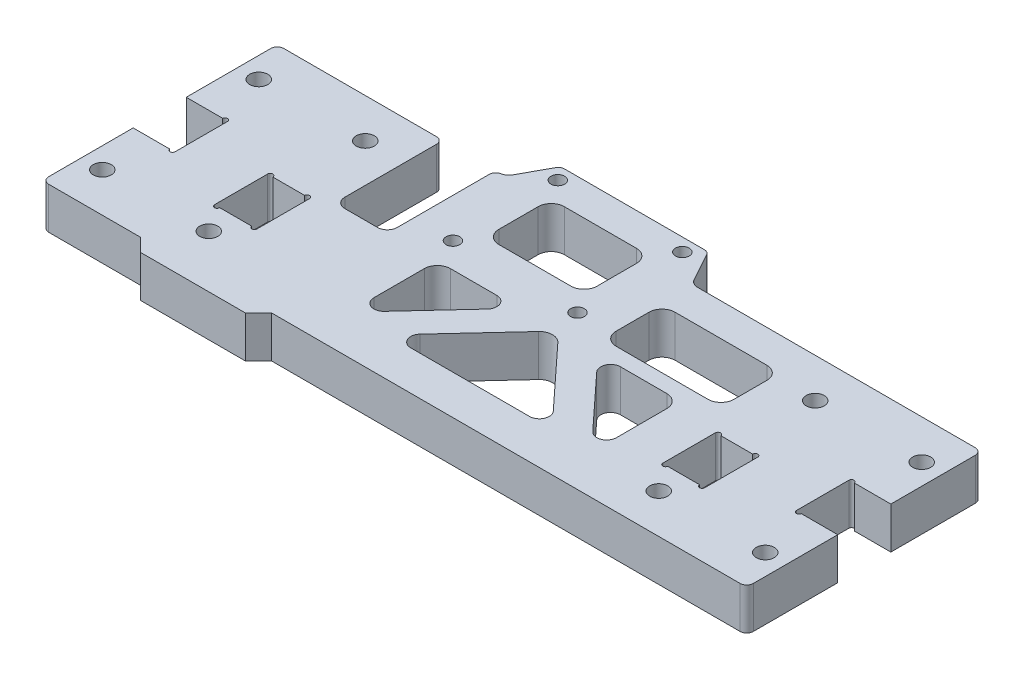
SolidWorks part; units mm, degrees
material "6061 Alloy"
ref_plane "Front Plane" through (0, 0, 0) normal (0, 0, 1) x (1, 0, 0)
ref_plane "Top Plane" through (0, 0, 0) normal (0, 1, 0) x (1, 0, 0)
ref_plane "Right Plane" through (0, 0, 0) normal (1, 0, 0) x (0, 0, -1)
sketch "Sketch1" plane through (0, 0, 0) normal (0, 1, 0) x (1, 0, 0)
  line L0 (107.5, 76.65) -> (107.5, 0) construction
  line L6 (32.7004, 36.1) -> (32.7004, 19.9)
  line L8 (45.6, 36) -> (45.6, 20)
  line L13 (0, 71.75) -> (69.5, 71.75)
  line L14 (69.5, 71.75) -> (75.5, 82.75)
  line L15 (75.5, 82.75) -> (120.5, 82.75)
  line L16 (120.5, 82.75) -> (126.5, 71.75)
  line L17 (126.5, 71.75) -> (215, 71.75)
  line L18 (32.7004, 28) -> (45.6, 28) construction
  line L19 (34.3004, 36.1) -> (44.0063, 36.1)
  line L20 (34.3004, 19.9) -> (44.0063, 19.9)
  line L21 (182.2996, 36.1) -> (182.2996, 19.9)
  line L22 (180.6996, 36.1) -> (170.9937, 36.1)
  line L23 (169.4, 36) -> (169.4, 20)
  line L24 (180.6996, 19.9) -> (170.9937, 19.9)
  line L25 (12.7, 35.875) -> (0, 35.875) construction
  line L29 (12.7, 43.975) -> (12.7, 27.775)
  line L30 (11.1189, 43.975) -> (0, 43.975)
  line L31 (11.1189, 27.775) -> (0, 27.775)
  line L32 (0, 27.775) -> (0, 0)
  line L33 (0, 43.975) -> (0, 71.75)
  line L34 (202.3, 35.875) -> (215, 35.875) construction
  line L35 (215, 43.975) -> (215, 71.75)
  line L36 (215, 27.775) -> (215, 0)
  line L37 (203.8811, 27.775) -> (215, 27.775)
  line L38 (203.8811, 43.975) -> (215, 43.975)
  line L39 (202.3, 43.975) -> (202.3, 27.775)
  line L40 (0, 0) -> (30, 0)
  line L41 (30, 0) -> (34, -4)
  line L42 (34, -4) -> (66, -4)
  line L43 (66, -4) -> (70, 0)
  line L44 (70, 0) -> (215, 0)
  circle A0 centre (38.85, 59.75) radius 2.75
  circle A5 centre (38.85, 12) radius 2.75
  circle A6 centre (176.15, 59.75) radius 2.75
  circle A7 centre (176.15, 12) radius 2.75
  arc A8 (32.7004, 36.1) -> (34.3004, 36.1) centre (33.5004, 36.1) cw
  arc A9 (45.6, 36) -> (44.0063, 36.1) centre (44.8, 36) ccw
  arc A10 (32.7004, 19.9) -> (34.3004, 19.9) centre (33.5004, 19.9) ccw
  arc A11 (45.6, 20) -> (44.0063, 19.9) centre (44.8, 20) cw
  arc A12 (182.2996, 19.9) -> (180.6996, 19.9) centre (181.4996, 19.9) cw
  arc A13 (182.2996, 36.1) -> (180.6996, 36.1) centre (181.4996, 36.1) ccw
  arc A14 (169.4, 36) -> (170.9937, 36.1) centre (170.2, 36) cw
  arc A15 (169.4, 20) -> (170.9937, 19.9) centre (170.2, 20) ccw
  circle A16 centre (6.35, 12) radius 2.75
  circle A17 centre (6.35, 59.75) radius 2.75
  arc A18 (12.7, 27.775) -> (11.1189, 27.775) centre (11.9095, 27.8976) cw
  arc A19 (12.7, 43.975) -> (11.1189, 43.975) centre (11.9095, 43.8524) ccw
  arc A20 (202.3, 43.975) -> (203.8811, 43.975) centre (203.0905, 43.8524) cw
  arc A21 (202.3, 27.775) -> (203.8811, 27.775) centre (203.0905, 27.8976) ccw
  circle A22 centre (208.65, 59.75) radius 2.75
  circle A23 centre (208.65, 12) radius 2.75
  dimension "D12" = 5.5
  dimension "D16" = 5.5
  dimension "D17" = 0.8
  dimension "D18" = 0.8
  dimension "D19" = 0.8
  dimension "D20" = 0.8
  dimension "D21" = 5.5
  dimension "D22" = 5.5
  dimension "D27" = 0.8
  dimension "D1" = 215
  dimension "D2" = 71.75
  dimension "D5" = 61.9
  dimension "D6" = 12.9
  dimension "D4" = 11
  dimension "D7" = 6
  dimension "D8" = 38
  dimension "D10" = 45
  dimension "D11" = 16.2
  dimension "D14" = 6
  dimension "D13" = 12
  dimension "D25" = 16.2
  dimension "D3" = 12
  dimension "D23" = 16.2
  dimension "D26" = 12.7
  dimension "D9" = 4
  dimension "D15" = 30
  dimension "D24" = 40
  dimension "D28" = 4
  dimension "D29" = 35.875
extrude "Boss-Extrude1" add sketch "Sketch1" along normal blind 12.7
sketch "Sketch2" plane through (0, 12.7, 0) normal (0, 1, 0) x (1, 0, 0)
  line L1 (50.6, 85.2461) -> (66.6, 85.2461)
  line L2 (50.6, 85.2461) -> (50.6, 38.75)
  line L3 (50.6, 38.75) -> (66.6, 38.75)
  line L4 (66.6, 85.2461) -> (66.6, 38.75)
  line L5 (45.6, 20) -> (45.6, 36) construction
  line L12 (69.5, 71.75) -> (0, 71.75) construction
  dimension "D1" = 5
  dimension "D2" = 16
  dimension "D3" = 33
extrude "Cut-Extrude1" cut sketch "Sketch2" against normal through all
sketch "Sketch3" plane through (0, 12.7, 0) normal (0, 1, 0) x (1, 0, 0)
  line L1 (66.6, 38.75) -> (66.6, 71.75) construction
  line L2 (120.5, 82.75) -> (75.5, 82.75) construction
  circle A0 centre (78.6, 78.75) radius 2.1
  circle A1 centre (78.6, 46.75) radius 2.1
  circle A2 centre (116.6, 78.75) radius 2.1
  circle A3 centre (116.6, 46.75) radius 2.1
  dimension "D2" = 4.2
  dimension "D5" = 4.2
  dimension "D8" = 32
  dimension "D1" = 4
  dimension "D3" = 12
  dimension "D4" = 32
  dimension "D7" = 38
  dimension "D6" = 2
extrude "Cut-Extrude2" cut sketch "Sketch3" against normal through all
sketch "Sketch5" plane through (0, 12.7, 0) normal (0, 1, 0) x (1, 0, 0)
  line L2 (86.8013, 17.6174) -> (101.935, 33.9618)
  line L3 (99.7337, 39) -> (85.6, 39)
  line L8 (81.6, 35) -> (81.6, 19.6556)
  line L12 (66.6, 38.75) -> (66.6, 71.75) construction
  line L13 (115.665, 35.8302) -> (98.265, 17.0382)
  line L14 (118.6, 39) -> (118.6, 12) construction
  line L15 (100.4663, 12) -> (136.7337, 12)
  line L16 (121.535, 35.8302) -> (138.935, 17.0382)
  line L17 (137.4663, 39) -> (151.6, 39)
  line L18 (150.3987, 17.6174) -> (135.265, 33.9618)
  line L19 (155.6, 35) -> (155.6, 19.6556)
  line L20 (120.5, 82.75) -> (75.5, 82.75) construction
  line L21 (86.6, 72.75) -> (108.6, 72.75)
  line L22 (82.6, 68.75) -> (82.6, 56.75)
  line L23 (86.6, 52.75) -> (108.6, 52.75)
  line L24 (112.6, 68.75) -> (112.6, 56.75)
  line L25 (215, 71.75) -> (126.5, 71.75) construction
  line L26 (131.4, 61.75) -> (159.4, 61.75)
  line L27 (127.4, 57.75) -> (127.4, 47.75)
  line L28 (131.4, 43.75) -> (159.4, 43.75)
  line L29 (163.4, 57.75) -> (163.4, 47.75)
  line L31 (169.4, 36) -> (169.4, 20) construction
  arc A0 (121.535, 35.8302) -> (115.665, 35.8302) centre (118.6, 33.1125) ccw
  arc A1 (155.6, 35) -> (151.6, 39) centre (151.6, 35) ccw
  arc A2 (81.6, 35) -> (85.6, 39) centre (85.6, 35) cw
  arc A3 (112.6, 68.75) -> (108.6, 72.75) centre (108.6, 68.75) ccw
  arc A4 (108.6, 52.75) -> (112.6, 56.75) centre (108.6, 56.75) ccw
  arc A5 (82.6, 56.75) -> (86.6, 52.75) centre (86.6, 56.75) ccw
  arc A6 (82.6, 68.75) -> (86.6, 72.75) centre (86.6, 68.75) cw
  arc A7 (150.3987, 17.6174) -> (155.6, 19.6556) centre (152.6, 19.6556) ccw
  arc A8 (135.265, 33.9618) -> (137.4663, 39) centre (137.4663, 36) cw
  arc A9 (86.8013, 17.6174) -> (81.6, 19.6556) centre (84.6, 19.6556) cw
  arc A10 (136.7337, 12) -> (138.935, 17.0382) centre (136.7337, 15) ccw
  arc A11 (100.4663, 12) -> (98.265, 17.0382) centre (100.4663, 15) cw
  arc A12 (101.935, 33.9618) -> (99.7337, 39) centre (99.7337, 36) ccw
  arc A13 (163.4, 57.75) -> (159.4, 61.75) centre (159.4, 57.75) ccw
  arc A14 (159.4, 43.75) -> (163.4, 47.75) centre (159.4, 47.75) ccw
  arc A15 (127.4, 47.75) -> (131.4, 43.75) centre (131.4, 47.75) ccw
  arc A16 (127.4, 57.75) -> (131.4, 61.75) centre (131.4, 57.75) cw
  point P25 (155.6, 39)
  point P28 (81.6, 39)
  point P33 (112.6, 52.75)
  point P36 (82.6, 52.75)
  point P39 (82.6, 72.75)
  point P42 (155.6, 12)
  point P45 (130.6, 39)
  point P48 (81.6, 12)
  point P51 (143.6, 12)
  point P54 (93.6, 12)
  point P57 (106.6, 39)
  point P68 (163.4, 61.75)
  point P71 (163.4, 43.75)
  point P76 (127.4, 61.75)
  dimension "D11" = 4
  dimension "D12" = 3
  dimension "D13" = 3
  dimension "D14" = 3
  dimension "D19" = 4
  dimension "D2" = 27
  dimension "D3" = 12
  dimension "D4" = 15
  dimension "D5" = 25
  dimension "D6" = 25
  dimension "D7" = 10
  dimension "D8" = 16
  dimension "D9" = 20
  dimension "D10" = 30
  dimension "D15" = 10
  dimension "D16" = 18
  dimension "D17" = 6
  dimension "D18" = 36
extrude "Cut-Extrude3" cut sketch "Sketch5" against normal through all
fillet "Fillet1" radius 3 4 edges at (69.5, 6.35, -71.75) (66.6, 6.35, -38.75) (50.6, 6.35, -38.75) (126.5, 6.35, -71.75)
fillet "Fillet2" radius 2 8 edges at (215, 6.35, -71.75) (120.5, 6.35, -82.75) (75.5, 6.35, -82.75) (50.6, 6.35, -71.75) (66.6, 6.35, -71.75) (0, 6.35, -71.75) (215, 6.35, 0) (0, 6.35, 0)
equation "\"DriveMotorLength\"= 90mm"
equation "\"DriveMotorGap\"= 10mm"
equation "\"AluminumThickness\"= 0.5in"
equation "\"ChassisWidth\"= ( \"DriveMotorLength\" + \"AluminumThickness\" ) * 2 + \"DriveMotorGap\""
equation "\"RepeatMagnumHoleWidth\"= 19.05mm"
equation "\"MortiseWidth\"= 16mm"
equation "\"ChassisScrewThruHole\"= 5.5mm"
equation "\"D11@Sketch1\"=\"MortiseSlotWidth\""
equation "\"D12@Sketch1\"=\"ChassisScrewThruHole\""
equation "\"D16@Sketch1\"=\"ChassisScrewThruHole\""
equation "\"MortiseSlotWidth\"= 16.2mm"
equation "\"Dogbone\"= 0.8mm"
equation "\"D17@Sketch1\"=\"Dogbone\""
equation "\"D18@Sketch1\"=\"Dogbone\""
equation "\"D19@Sketch1\"=\"Dogbone\""
equation "\"D20@Sketch1\"=\"Dogbone\""
equation "\"D21@Sketch1\"=\"ChassisScrewThruHole\""
equation "\"D22@Sketch1\"=\"ChassisScrewThruHole\""
equation "\"D27@Sketch1\"=\"Dogbone\""
equation "\"D23@Sketch1\"=\"MortiseSlotWidth\""
equation "\"D25@Sketch1\"=\"MortiseSlotWidth\""
